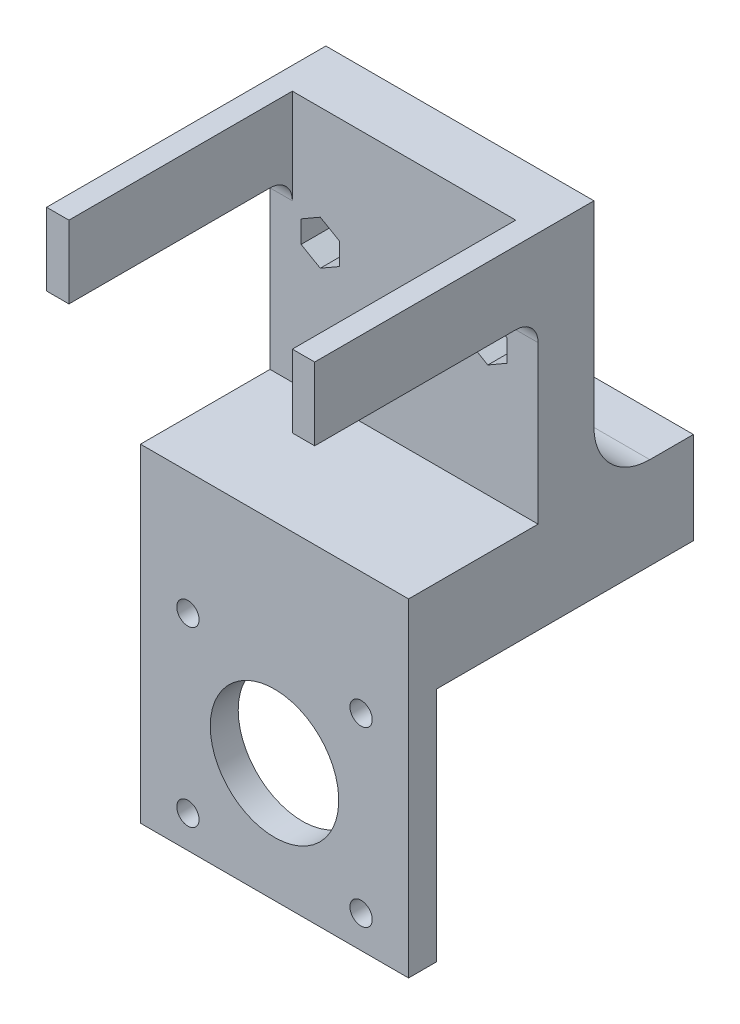
SolidWorks part; units mm, degrees
ref_plane "Front Plane" through (0, 0, 0) normal (0, 0, 1) x (1, 0, 0)
ref_plane "Top Plane" through (0, 0, 0) normal (0, 1, 0) x (1, 0, 0)
ref_plane "Right Plane" through (0, 0, 0) normal (1, 0, 0) x (0, 0, -1)
sketch "Sketch1" plane through (0, 0, 0) normal (0, 0, 1) x (1, 0, 0)
  line L1 (0, 0) -> (48, 0)
  line L2 (0, 0) -> (0, 53)
  line L3 (0, 53) -> (48, 53)
  line L4 (48, 0) -> (48, 53)
  dimension "D1" = 53
  dimension "D2" = 48
extrude "Boss-Extrude1" add sketch "Sketch1" along normal blind 10
sketch "Sketch2" plane through (0, 0, 0) normal (0, 0, -1) x (-1, 0, 0)
  line L0 (0, 53) -> (0, 0) construction
  line L1 (-48, 0) -> (0, 0)
  line L2 (-48, 0) -> (-48, -5.6163)
  line L3 (-48, -5.6163) -> (0, -5.6163)
  line L4 (0, 0) -> (0, -5.6163)
  dimension "D1" = 5.6163
extrude "Boss-Extrude2" add sketch "Sketch2" against normal blind 33.1918
sketch "Sketch4" plane through (0, 0, 10) normal (0, 0, 1) x (1, 0, 0)
  line L1 (0, 53) -> (4, 53)
  line L2 (0, 53) -> (0, 43)
  line L3 (0, 43) -> (4, 43)
  line L4 (4, 53) -> (4, 43)
  line L5 (48, 53) -> (44, 53)
  line L6 (48, 53) -> (48, 43)
  line L7 (48, 43) -> (44, 43)
  line L8 (44, 53) -> (44, 43)
  dimension "D1" = 10
  dimension "D2" = 4
extrude "Boss-Extrude4" add sketch "Sketch4" along normal blind 40
sketch "Sketch5" plane through (0, 0, 10) normal (0, 0, 1) x (1, 0, 0)
  line L0 (48, 0) -> (48, 43) construction
  line L1 (0, 0) -> (48, 0)
  line L2 (0, 0) -> (0, 10.8609)
  line L3 (0, 10.8609) -> (48, 10.8609)
  line L4 (48, 0) -> (48, 10.8609)
  dimension "D1" = 10.8609
extrude "Boss-Extrude5" add sketch "Sketch5" along normal up to surface (23.1918 mm away) up to face at (24, -2.8082, 33.1918)
sketch "Sketch6" plane through (0, -5.6163, 0) normal (0, -1, 0) x (1, 0, 0)
  line L0 (0, 0) -> (0, 28.1918) construction
  line L1 (0, 33.1918) -> (0, 0) construction
  line L2 (48, 33.1918) -> (48, 0) construction
  line L3 (0, 28.1918) -> (48, 28.1918)
  line L4 (0, 28.1918) -> (0, 33.1918)
  line L5 (0, 33.1918) -> (48, 33.1918)
  line L6 (48, 28.1918) -> (48, 33.1918)
  line L8 (48, 33.1918) -> (0, 33.1918) construction
  dimension "D2" = 5
extrude "Boss-Extrude6" add sketch "Sketch6" along normal blind 42.3
sketch "Sketch7" plane through (0, 0, 0) normal (-1, 0, 0) x (0, 0, 1)
  line L0 (33.1918, 10.8609) -> (10, 10.8609) construction
  line L1 (0, -5.6163) -> (-12.8082, -5.6163)
  line L2 (0, -5.6163) -> (0, 10.8609)
  line L3 (0, 10.8609) -> (-12.8082, 10.8609)
  line L4 (-12.8082, -5.6163) -> (-12.8082, 10.8609)
  line L5 (28.1918, -47.9163) -> (28.1918, -5.6163) construction
  dimension "D1" = 41
extrude "Boss-Extrude7" add sketch "Sketch7" against normal up to surface (48 mm away) up to face at (48, 10.6657, 24.2767)
sketch "Sketch8" plane through (0, 0, 28.1918) normal (0, 0, -1) x (-1, 0, 0)
  line L0 (-24, -26.6163) -> (-24, -5.6163) construction
  line L1 (0, -5.6163) -> (-48, -5.6163) construction
  line L3 (-8.5, -42.1163) -> (-39.5, -42.1163) construction
  line L4 (-8.5, -42.1163) -> (-8.5, -11.1163) construction
  line L5 (-8.5, -11.1163) -> (-39.5, -11.1163) construction
  line L6 (-39.5, -42.1163) -> (-39.5, -11.1163) construction
  line L7 (-8.5, -42.1163) -> (-39.5, -11.1163) construction
  line L8 (-8.5, -11.1163) -> (-39.5, -42.1163) construction
  circle A0 centre (-24, -26.6163) radius 11.5
  circle A1 centre (-39.5, -11.1163) radius 2
  circle A2 centre (-39.5, -42.1163) radius 2
  circle A3 centre (-8.5, -11.1163) radius 2
  circle A4 centre (-8.5, -42.1163) radius 2
  dimension "D2" = 23
  dimension "D4" = 4
  dimension "D1" = 21
  dimension "D3" = 31
extrude "Cut-Extrude1" cut sketch "Sketch8" against normal up to next
fillet "Fillet1" radius 10 1 edges at (24, 10.8609, 0)
fillet "Fillet2" radius 4 2 edges at (2, 43, 10) (46, 43, 10)
sketch "Sketch9" plane through (48, 0, 0) normal (1, 0, 0) x (0, 0, -1)
  line L1 (12.8082, 10.8609) -> (17.8082, 10.8609)
  line L2 (12.8082, 10.8609) -> (12.8082, -5.6163)
  line L3 (12.8082, -5.6163) -> (17.8082, -5.6163)
  line L4 (17.8082, 10.8609) -> (17.8082, -5.6163)
  line L5 (-28.1918, -5.6163) -> (12.8082, -5.6163) construction
  dimension "D1" = 5
extrude "Boss-Extrude9" add sketch "Sketch9" against normal up to surface (48 mm away) contours L4 L3 L2 L1 up to face at (0, 13.3569, 15.8852)
sketch "Sketch10" plane through (0, 0, 10) normal (0, 0, 1) x (1, 0, 0)
  line L0 (4, 53) -> (9, 35) construction
  line L1 (9, 35) -> (39, 35) construction
  line L2 (39, 35) -> (44, 53) construction
  line L3 (44, 53) -> (4, 53) construction
  line L4 (44, 53) -> (44, 43) construction
  line L6 (12.429, 36.9797) -> (9, 38.9595)
  line L7 (9, 38.9595) -> (5.571, 36.9797)
  line L8 (5.571, 36.9797) -> (5.571, 33.0203)
  line L9 (5.571, 33.0203) -> (9, 31.0405)
  line L10 (9, 31.0405) -> (12.429, 33.0203)
  line L11 (12.429, 33.0203) -> (12.429, 36.9797)
  line L12 (35.571, 36.9797) -> (35.571, 33.0203)
  line L13 (35.571, 33.0203) -> (39, 31.0405)
  line L14 (39, 31.0405) -> (42.429, 33.0203)
  line L15 (42.429, 33.0203) -> (42.429, 36.9797)
  line L16 (42.429, 36.9797) -> (39, 38.9595)
  line L17 (39, 38.9595) -> (35.571, 36.9797)
  circle A0 centre (9, 35) radius 3.429 construction
  circle A1 centre (39, 35) radius 3.429 construction
  dimension "D1" = 6.858
  dimension "D2" = 30
  dimension "D3" = 18
extrude "Cut-Extrude2" cut sketch "Sketch10" against normal blind 6
sketch "Sketch11" plane through (0, 0, 4) normal (0, 0, 1) x (1, 0, 0)
  circle A0 centre (9, 35) radius 1.9304
  circle A1 centre (39, 35) radius 1.9304
  dimension "D1" = 3.8608
extrude "Cut-Extrude3" cut sketch "Sketch11" against normal blind 6
sketch "Sketch12" plane through (0, 53, 0) normal (0, 1, 0) x (1, 0, 0)
  line L0 (0, 0) -> (0, -50)
  line L1 (0, -50) -> (4, -50)
  line L2 (4, -50) -> (4, -10)
  line L3 (4, -10) -> (44, -10)
  line L4 (44, -10) -> (44, -50)
  line L5 (44, -50) -> (48, -50)
  line L6 (48, -50) -> (48, 0)
  line L7 (48, 0) -> (0, 0)
extrude "Boss-Extrude11" add sketch "Sketch12" along normal blind 3
